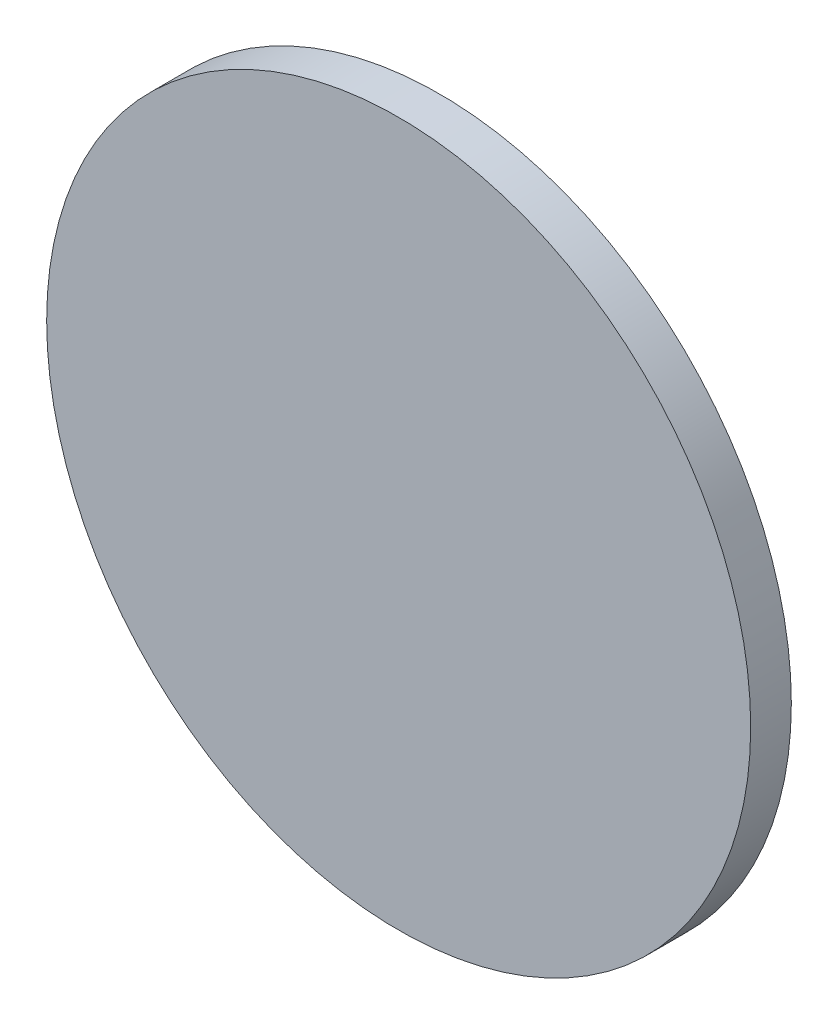
SolidWorks part; units mm, degrees
material "Acrylic (Medium-high impact)"
ref_plane "X-Y Datum" through (0, 0, 0) normal (0, 0, 1) x (1, 0, 0)
ref_plane "X-Z Datum" through (0, 0, 0) normal (0, 1, 0) x (1, 0, 0)
ref_plane "Y-Z Datum" through (0, 0, 0) normal (1, 0, 0) x (0, 0, -1)
sketch "Sketch1" plane through (0, 0, 0) normal (0, 0, 1) x (1, 0, 0)
  circle A0 centre (0, 0) radius 27.5
  dimension "D1" = 55
extrude "Boss-Extrude1" add sketch "Sketch1" along normal blind 3.175
